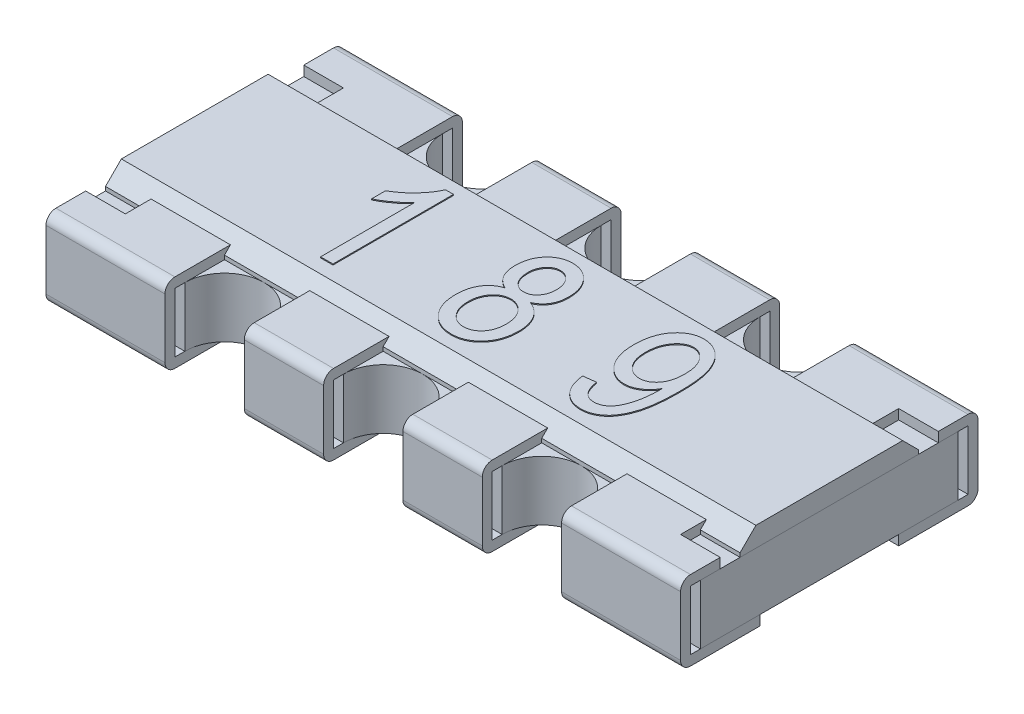
SolidWorks part; units mm, degrees
material "E-Glass Fiber"
ref_plane "Front Plane" through (0, 0, 0) normal (0, 0, 1) x (1, 0, 0)
ref_plane "Top Plane" through (0, 0, 0) normal (0, 1, 0) x (1, 0, 0)
ref_plane "Right Plane" through (0, 0, 0) normal (1, 0, 0) x (0, 0, -1)
sketch "Sketch5" plane through (0, 0, 0) normal (1, 0, 0) x (0, 0, -1)
  line L0 (55, 0) -> (-55, 0) construction
  line L1 (-0.7, 0.4) -> (0.7, 0.4)
  line L2 (-0.75, 0.35) -> (-0.75, 0.05)
  line L3 (-0.7, 0) -> (-0.35, 0)
  line L4 (0.75, 0.35) -> (0.75, 0.05)
  line L5 (0, 55) -> (0, -55) construction
  line L8 (0.35, 0) -> (0.7, 0)
  arc A0 (0.7, 0.4) -> (0.75, 0.35) centre (0.7, 0.35) cw
  arc A1 (0.7, 0) -> (0.75, 0.05) centre (0.7, 0.05) ccw
  arc A2 (-0.75, 0.05) -> (-0.7, 0) centre (-0.7, 0.05) ccw
  arc A3 (-0.7, 0.4) -> (-0.75, 0.35) centre (-0.7, 0.35) ccw
  point P10 (0.75, 0.4)
  point P13 (0.75, 0)
  point P18 (-0.75, 0.4)
  dimension "D4" = 0.05
  dimension "D1" = 0.4
  dimension "D2" = 1.5
  dimension "D3" = 0.75
  dimension "D5" = 0.4
  dimension "D6" = 0.4
extrude "Extrude-Thin1" add sketch "Sketch5" along normal mid plane 3.2 thin thin type one direction reverse wall 0.05
sketch "Sketch6" plane through (0, 0.4, 0) normal (0, 1, 0) x (1, 0, 0)
  line L1 (1.6, 0.75) -> (-1.6, 0.75) construction
  line L2 (-1, 0.75) -> (-0.6, 0.75)
  line L3 (-1, 0.75) -> (-1, 0.25)
  line L4 (-1, 0.25) -> (-0.6, 0.25)
  line L6 (-0.6, 0.75) -> (-0.6, 0.25)
  line L7 (0, -0.22) -> (0, 0.22) construction
  line L8 (-0.2, 0.75) -> (0.2, 0.75)
  line L9 (-0.2, 0.75) -> (-0.2, 0.25)
  line L10 (-0.2, 0.25) -> (0.2, 0.25)
  line L11 (0.2, 0.75) -> (0.2, 0.25)
  line L12 (0.6, 0.75) -> (1, 0.75)
  line L13 (0.6, 0.75) -> (0.6, 0.25)
  line L14 (0.6, 0.25) -> (1, 0.25)
  line L15 (1, 0.75) -> (1, 0.25)
  line L16 (1.6, 0.7) -> (1.6, -0.7) construction
  line L18 (1.6, -0.75) -> (-1.6, -0.75) construction
  line L19 (-1, -0.75) -> (-0.6, -0.75)
  line L20 (-1, -0.75) -> (-1, -0.25)
  line L21 (-1, -0.25) -> (-0.6, -0.25)
  line L22 (-0.6, -0.75) -> (-0.6, -0.25)
  line L24 (-0.2, -0.75) -> (0.2, -0.75)
  line L25 (-0.2, -0.75) -> (-0.2, -0.25)
  line L26 (-0.2, -0.25) -> (0.2, -0.25)
  line L27 (0.2, -0.75) -> (0.2, -0.25)
  line L28 (0.6, -0.75) -> (1, -0.75)
  line L29 (0.6, -0.75) -> (0.6, -0.25)
  line L30 (0.6, -0.25) -> (1, -0.25)
  line L31 (1, -0.75) -> (1, -0.25)
  dimension "D1" = 0.5
  dimension "D2" = 0.4
  dimension "D3" = 0.8
  dimension "D4" = 0.2
  dimension "D5" = 0.8
  dimension "D6" = 0.4
  dimension "D7" = 0.4
  dimension "D8" = 0.6
extrude "Cut-Extrude3" cut sketch "Sketch6" against normal through all
sketch "Sketch7" plane through (0, 0.4, 0) normal (0, 1, 0) x (1, 0, 0)
  line L0 (-1.6, 0.7) -> (-1.6, -0.7) construction
  line L1 (-1.6, -0.55) -> (-1.4, -0.55)
  line L2 (-1.6, -0.55) -> (-1.6, 0.55)
  line L3 (-1.6, 0.55) -> (-1.4, 0.55)
  line L4 (-1.4, -0.55) -> (-1.4, 0.55)
  line L5 (1.6, 0.7) -> (1.6, -0.7) construction
  line L6 (1.6, -0.55) -> (1.4, -0.55)
  line L7 (1.6, -0.55) -> (1.6, 0.55)
  line L8 (1.6, 0.55) -> (1.4, 0.55)
  line L9 (1.4, -0.55) -> (1.4, 0.55)
  line L12 (-0.22, 0) -> (0.22, 0) construction
  dimension "D1" = 0.55
  dimension "D2" = 1.1
  dimension "D3" = 0.2
extrude "Cut-Extrude4" cut sketch "Sketch7" against normal blind 0.1
sketch "Sketch1" plane through (0, 0.05, 0) normal (0, 1, 0) x (1, 0, 0)
  line L0 (-1.6, -0.65) -> (1.6, 0.65) construction
  line L1 (-1.6, 0.65) -> (1.6, 0.65)
  line L2 (-1.6, 0.65) -> (-1.6, -0.65)
  line L3 (-1.6, -0.65) -> (1.6, -0.65)
  line L4 (1.6, 0.65) -> (1.6, -0.65)
  line L5 (-1.2, 0.65) -> (-1.2, -0.65) construction
  line L6 (-1.6, 0.45) -> (1.6, 0.45) construction
  line L7 (-0.4, 0.65) -> (-0.4, -0.65) construction
  line L8 (-1.6, -0.45) -> (1.6, -0.45) construction
  line L9 (0.4, 0.65) -> (0.4, -0.65) construction
  line L10 (0, -0.22) -> (0, 0.22) construction
  line L11 (1.2, 0.65) -> (1.2, -0.65) construction
  dimension "D3" = 0.2
  dimension "D1" = 3.2
  dimension "D2" = 1.3
  dimension "D4" = 0.2
  dimension "D5" = 0.8
  dimension "D6" = 0.8
  dimension "D7" = 0.8
  dimension "D8" = 0.4
extrude "Boss-Extrude3" add sketch "Sketch1" along normal blind 0.3 separate body
sketch "Sketch9" plane through (0, 0.35, 0) normal (0, 1, 0) x (1, 0, 0)
  line L1 (-1.6, 0.45) -> (1.6, 0.45)
  line L2 (-1.6, 0.45) -> (-1.6, -0.45)
  line L3 (-1.6, -0.45) -> (1.6, -0.45)
  line L4 (1.6, 0.45) -> (1.6, -0.45)
extrude "Boss-Extrude4" add sketch "Sketch9" along normal blind 0.1
chamfer "Chamfer1" distance 0.08 angle 45 2 edges at (0, 0.45, 0.45) (0, 0.45, -0.45)
sketch "Sketch10" plane through (0, 0.05, 0) normal (0, 1, 0) x (1, 0, 0)
  line L0 (-1.6, 0.65) -> (1.6, 0.65) construction
  line L1 (-1.6, -0.65) -> (1.6, -0.65) construction
  line L2 (0, -0.2475) -> (0, 0.2475) construction
  circle A0 centre (-0.8, 0.65) radius 0.2
  circle A1 centre (0, 0.65) radius 0.2
  circle A2 centre (0.8, 0.65) radius 0.2
  circle A3 centre (0.8, -0.65) radius 0.2
  circle A4 centre (0, -0.65) radius 0.2
  circle A5 centre (-0.8, -0.65) radius 0.2
  dimension "D3" = 0.4
  dimension "D1" = 0.8
  dimension "D2" = 0.8
extrude "Cut-Extrude7" cut sketch "Sketch10" along normal blind 5
sketch "Sketch11" plane through (0, 0.45, 0) normal (0, 1, 0) x (1, 0, 0)
  line L0 (0, -0.2475) -> (0, 0.2475) construction
  line L2 (-0.2475, 0) -> (0.2475, 0) construction
  text T0 "1 8 9\r\n" font "Arial Narrow" height 0.6
  dimension "D1" = 0.86
  dimension "D2" = 0.3
extrude "Boss-Extrude5" add sketch "Sketch11" along normal blind 0.005
ref_plane "Plane1" through (-1.2, 0, 0) normal (1, 0, 0) x (0, 0, -1)
